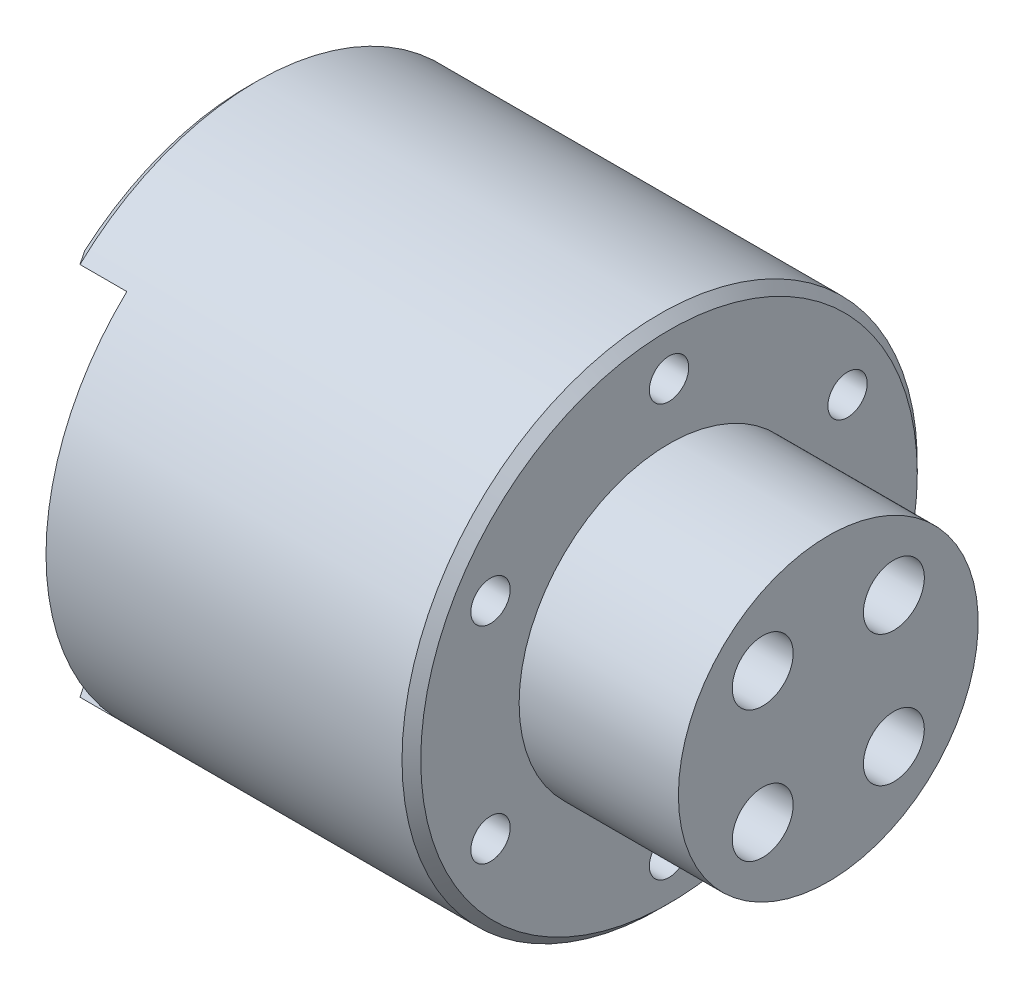
SolidWorks part; units mm, degrees
material "1023 Carbon Steel Sheet (SS)"
ref_plane "Front Plane" through (0, 0, 0) normal (0, 0, 1) x (1, 0, 0)
ref_plane "Top Plane" through (0, 0, 0) normal (0, 1, 0) x (1, 0, 0)
ref_plane "Right Plane" through (0, 0, 0) normal (1, 0, 0) x (0, 0, -1)
sketch "Sketch1" plane through (0, 0, 0) normal (0, 0, 1) x (1, 0, 0)
  line L0 (0, 0) -> (221.0251, 0) construction
  line L1 (55, 0) -> (-55, 0) construction
  line L2 (0, 0) -> (0, 27.5)
  line L3 (0, -55) -> (0, 55) construction
  line L4 (0, 27.5) -> (45, 27.5)
  line L13 (45, 27.5) -> (45, 16)
  line L14 (62, 0) -> (0, 0)
  line L15 (45, 16) -> (62, 16)
  line L16 (62, 16) -> (62, 0)
  dimension "D1" = 45
  dimension "D2" = 55
  dimension "D3" = 32
  dimension "D4" = 17
revolve "Revolve1" add sketch "Sketch1" angle 360 about L0
ref_axis "Axis1" through (45, 0, 0) along (-1, 0, 0)
sketch "Sketch2" plane through (0, 0, 0) normal (-1, 0, 0) x (0, 0, 1)
  line L0 (0, -18.7) -> (0, 18.7) construction
  line L1 (55, 0) -> (-55, 0) construction
  circle A0 centre (-7, 7) radius 3.25
  circle A1 centre (7, 7) radius 3.25
  circle A2 centre (7, -7) radius 3.25
  circle A3 centre (-7, -7) radius 3.25
  dimension "D3" = 6.5
  dimension "D1" = 14
  dimension "D2" = 14
extrude "Cut-Extrude1" cut sketch "Sketch2" against normal through all
sketch "Sketch3" plane through (45, 0, 0) normal (1, 0, 0) x (0, 0, -1)
  line L0 (0, 18.7) -> (0, -18.7) construction
  line L1 (55, 0) -> (-55, 0) construction
  circle A0 centre (0, 22) radius 2.1
  dimension "D1" = 4.2
  dimension "D2" = 22
extrude "Cut-Extrude2" cut sketch "Sketch3" against normal blind 20
cosmetic thread "Cosmetic Thread5" parameters "D1"=15, "D2"=5
pattern_circular "CirPattern1" count 6 every 60 about axis through (45, 0, 0) along (-1, 0, 0) of "Cut-Extrude2" reverse direction yes
cosmetic thread "Cosmetic Thread6" parameters "D1"=15, "D2"=5
cosmetic thread "Cosmetic Thread7" parameters "D1"=15, "D2"=5
cosmetic thread "Cosmetic Thread8" parameters "D1"=15, "D2"=5
cosmetic thread "Cosmetic Thread9" parameters "D1"=15, "D2"=5
cosmetic thread "Cosmetic Thread10" parameters "D1"=15, "D2"=5
chamfer "Chamfer1" distance 1 angle 45 6 edges at (0, 0, 27.5) (45, 0, 27.5) (0, 7, -3.75) (0, 7, 3.75) (0, -7, 10.25) (0, -7, -10.25)
sketch "Sketch4" plane through (0, 0, 0) normal (-1, 0, 0) x (0, 0, 1)
  line L0 (-18.8746, 20) -> (18.8746, 20)
  line L1 (55, 0) -> (-55, 0) construction
  line L2 (-18.8746, -20) -> (18.8746, -20)
  circle A0 centre (0, 0) radius 27.5 construction
  arc A1 (-18.8746, 20) -> (-18.8746, -20) centre (0, 0) ccw
  arc A2 (18.8746, -20) -> (18.8746, 20) centre (0, 0) ccw
  dimension "D1" = 40
extrude "Cut-Extrude3" cut sketch "Sketch4" against normal blind 6
